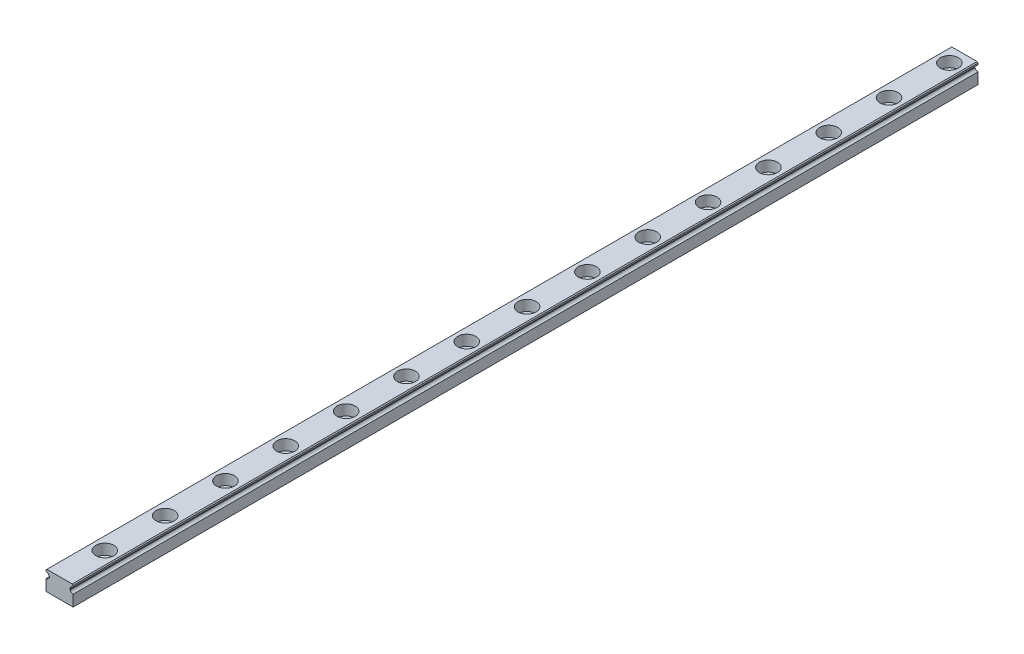
SolidWorks part; units mm, degrees
ref_plane "Спереди" through (0, 0, 0) normal (0, 0, 1) x (1, 0, 0)
ref_plane "Сверху" through (0, 0, 0) normal (0, 1, 0) x (1, 0, 0)
ref_plane "Справа" through (0, 0, 0) normal (1, 0, 0) x (0, 0, -1)
sketch "Sketch1" plane through (0, 0, 0) normal (0, 0, 1) x (1, 0, 0)
  line L0 (0, 0) -> (0, 5.7299) construction
  line L1 (-4.5, -3.25) -> (4.5, -3.25)
  line L2 (-4.5, -3.25) -> (-4.5, 0.45)
  line L3 (-4.5, 3.25) -> (4.5, 3.25)
  line L4 (4.5, -3.25) -> (4.5, 0.45)
  line L5 (-4.5, -3.25) -> (4.5, 3.25) construction
  line L6 (-4.5, 3.25) -> (4.5, -3.25) construction
  line L7 (-4.5, 2.45) -> (-4.5, 3.25)
  line L8 (-3.5318, 1.2) -> (-3.4, 1.2)
  line L9 (3.5318, 1.2) -> (3.4, 1.2)
  line L10 (-3.5318, 1.7) -> (-3.4, 1.7)
  line L11 (-3.4, 1.2) -> (-3.4, 1.7)
  line L12 (3.4, 1.2) -> (3.4, 1.7)
  line L13 (3.5318, 1.7) -> (3.4, 1.7)
  line L14 (4.5, 2.45) -> (4.5, 3.25)
  line L15 (-3.4, 1.45) -> (-4.5, 1.45) construction
  arc A0 (-3.5318, 1.7) -> (-4.5, 2.45) centre (-4.5, 1.45) ccw
  arc A1 (-4.5, 0.45) -> (-3.5318, 1.2) centre (-4.5, 1.45) ccw
  arc A2 (4.5, 0.45) -> (3.5318, 1.2) centre (4.5, 1.45) cw
  arc A3 (3.5318, 1.7) -> (4.5, 2.45) centre (4.5, 1.45) cw
  point P0 (0, 0)
  dimension "D3" = 1
  dimension "D1" = 9
  dimension "D2" = 6.5
  dimension "D4" = 2.05
  dimension "D5" = 6.8
  dimension "D6" = 0.5
extrude "Extrude1" add sketch "Sketch1" along normal blind 300
sketch "Sketch2" plane through (0, 3.25, 0) normal (0, 1, 0) x (1, 0, 0)
  line L0 (4.5, 0) -> (-4.5, 0) construction
  circle A0 centre (0, -5) radius 1.75
  circle A1 centre (0, -5) radius 3
  dimension "D1" = 3.5
  dimension "D2" = 6
  dimension "D3" = 5
extrude "Extrude2" cut sketch "Sketch2" against normal blind 3.5 contours A1
extrude "Extrude3" cut sketch "Sketch" against normal through all contours A0
sketch "Sketch" plane through (0, 3.25, 0) normal (0, 1, 0) x (1, 0, 0) same geometry as "Sketch2"
pattern_linear "LPattern1" count 40 spacing 20 along (0, 0, 1) of "Extrude2", "Extrude3"
chamfer "Chamfer1" distance 0.3 angle 45 2 edges at (4.5, 3.25, 150) (-4.5, 3.25, 150)
